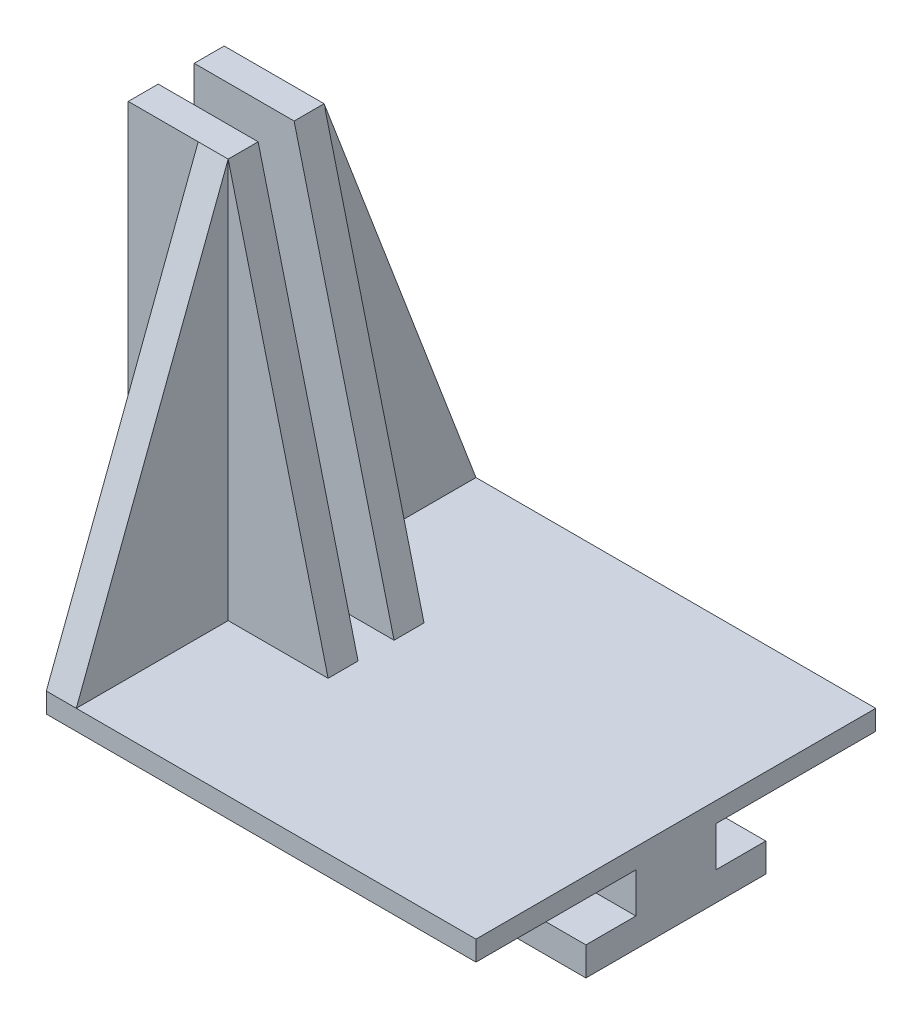
SolidWorks part; units mm, degrees
ref_plane "Front Plane" through (0, 0, 0) normal (0, 0, 1) x (1, 0, 0)
ref_plane "Top Plane" through (0, 0, 0) normal (0, 1, 0) x (1, 0, 0)
ref_plane "Right Plane" through (0, 0, 0) normal (1, 0, 0) x (0, 0, -1)
sketch "Sketch1" plane through (0, 0, 0) normal (0, 1, 0) x (1, 0, 0)
  line L1 (10, 10) -> (-10, 10)
  line L2 (10, 10) -> (10, -10)
  line L3 (10, -10) -> (-10, -10)
  line L4 (-10, 10) -> (-10, -10)
  line L5 (10, 10) -> (-10, -10) construction
  line L6 (10, -10) -> (-10, 10) construction
  point P0 (0, 0)
  dimension "D1" = 20
  dimension "D2" = 20
extrude "Boss-Extrude1" add sketch "Sketch1" along normal blind 1
sketch "Sketch4" plane through (10, 0, 0) normal (1, 0, 0) x (0, 0, -1)
  line L0 (-2, 0) -> (-2, -2)
  line L1 (-10, 0) -> (10, 0) construction
  line L2 (-2, -2) -> (-4.5, -2)
  line L3 (-4.5, -2) -> (-4.5, -3.4361)
  line L4 (-4.5, -3.4361) -> (4.5, -3.4361)
  line L5 (4.5, -3.4361) -> (4.5, -2)
  line L6 (4.5, -2) -> (2, -2)
  line L7 (2, -2) -> (2, 0)
  line L8 (-2, 0) -> (2, 0)
  dimension "D1" = 2
  dimension "D2" = 2
  dimension "D4" = 2.5
extrude "Boss-Extrude5" add sketch "Sketch4" against normal blind 20 contours L2 L3 L4 L5 L6 L7 L8 L0
sketch "Sketch5" plane through (-10, 0, 0) normal (-1, 0, 0) x (0, 0, 1)
  line L0 (0, 1) -> (0, 6.0182) construction
  line L2 (-0.9, 1) -> (-0.9, 21)
  line L3 (-10, 1) -> (10, 1) construction
  line L4 (-0.9, 21) -> (-2.4, 21)
  line L5 (-2.4, 21) -> (-2.4, 1)
  line L6 (-2.4, 1) -> (-0.9, 1)
  line L7 (-2.4, 21) -> (-10, 1)
  line L8 (-10, 1) -> (-10, 0)
  line L9 (-10, 0) -> (-0.9, 0)
  line L10 (-0.9, 0) -> (-0.9, 1)
  line L11 (-2.4, 1) -> (-2.4, 21)
  line M1 (-10, 0) -> (-2, 0)
  line M11 (10, 1) -> (-10, 1)
  line M12 (-10, 1) -> (-10, 0)
  dimension "D1" = 1.5
  dimension "D2" = 20
  dimension "D3" = 0.9
extrude "Boss-Extrude6" add sketch "Sketch5" along normal blind 5 and the other way blind 5 separate body contours L4 L5 L2 M11 region at (-10, 11, -1.65)
sketch "Sketch6" plane through (0, 0, -0.9) normal (0, 0, 1) x (1, 0, 0)
  line L0 (-5, 1) -> (-10, 21)
  line L1 (-5, 21) -> (-15, 21) construction
  line L2 (-10, 21) -> (-5, 21)
  line L4 (-5, 21) -> (-5, 1)
extrude "Cut-Extrude1" cut sketch "Sketch6" against normal blind 5
extrude "Boss-Extrude7" add sketch "Sketch5<3>" along normal blind 1.5 contours L5 L7 M11 | L9 L10 M11 M12 M1 region at (-10, 0.5, -5.45) region at (-10, 7.6667, -4.9333)
sketch "Sketch5<3>" plane through (-10, 0, 0) normal (-1, 0, 0) x (0, 0, 1) same geometry as "Sketch5"
mirror "Mirror5" about plane through (0, 0, 0) normal (0, 0, 1) of bodies 112
